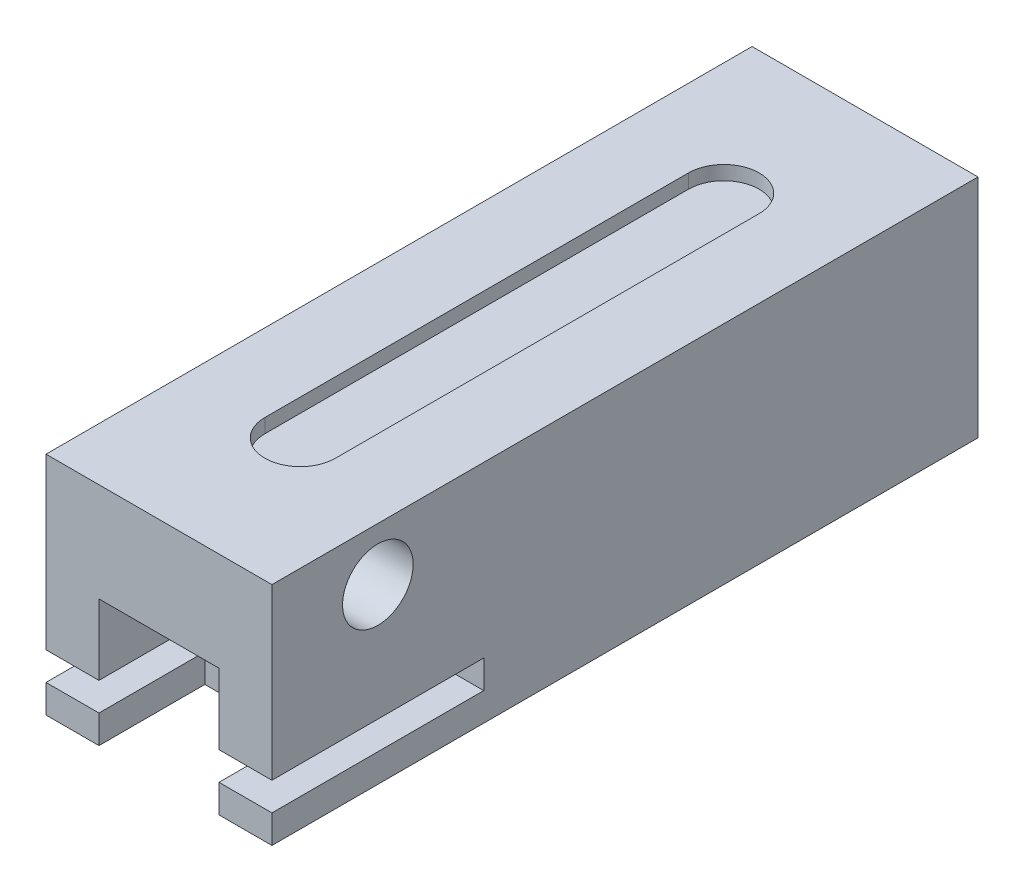
SolidWorks part; units mm, degrees
ref_plane "Front Plane" through (0, 0, 0) normal (0, 0, 1) x (1, 0, 0)
ref_plane "Top Plane" through (0, 0, 0) normal (0, 1, 0) x (1, 0, 0)
ref_plane "Right Plane" through (0, 0, 0) normal (1, 0, 0) x (0, 0, -1)
sketch "Sketch1" plane through (0, 0, 0) normal (0, 0, 1) x (1, 0, 0)
  line L1 (-16, -16) -> (16, -16)
  line L2 (-16, -16) -> (-16, 16)
  line L3 (-16, 16) -> (16, 16)
  line L4 (16, -16) -> (16, 16)
  line L5 (-16, -16) -> (16, 16) construction
  line L6 (-16, 16) -> (16, -16) construction
  point P0 (0, 0)
  dimension "D1" = 32
  dimension "D2" = 32
extrude "Boss-Extrude1" add sketch "Sketch1" against normal blind 100
sketch "Sketch2" plane through (0, 0, 0) normal (0, 1, 0) x (1, 0, 0)
  line L0 (0, 20) -> (0, 0) construction
  line L1 (0, 20) -> (0, 80) construction
  line L2 (5, 80) -> (5, 20)
  line L3 (-5, 80) -> (-5, 20)
  circle A0 centre (0, 20) radius 5
  circle A1 centre (0, 80) radius 5
  point P10 (-11.9537, 28.2218)
  point P11 (11.5572, 27.3906)
  point P12 (0, 0)
  dimension "D1" = 10
  dimension "D2" = 10
  dimension "D3" = 20
  dimension "D4" = 60
extrude "Cut-Extrude1" cut sketch "Sketch2" against normal blind 2 from surface contours A1 L3 A0 L2 | A1 | A0 region at (0, 0, -80) region at (0, 0, -50) region at (0, 0, -20) starting at face at (0, 16, -50)
sketch "Sketch3" plane through (0, 0, 0) normal (0, 0, 1) x (1, 0, 0)
  line L0 (-16, 16) -> (-16, -16) construction
  line L1 (-16, -8) -> (16, -8)
  line L2 (-16, -8) -> (-16, -12)
  line L3 (-16, -12) -> (16, -12)
  line L4 (16, -8) -> (16, -12)
  line L5 (16, -16) -> (16, 16) construction
  line L6 (0, -22.0014) -> (0, -12) construction
  line L7 (-8.5, -12) -> (8.5, -12)
  line L8 (-8.5, -12) -> (-8.5, -22.0014)
  line L9 (-8.5, -22.0014) -> (8.5, -22.0014)
  line L10 (8.5, -12) -> (8.5, -22.0014)
  line L11 (-16, -16) -> (16, -16) construction
  line L12 (-8.5, -8) -> (8.5, -8)
  line L13 (-8.5, -8) -> (-8.5, 2)
  line L14 (-8.5, 2) -> (8.5, 2)
  line L15 (8.5, -8) -> (8.5, 2)
  point P14 (0, -12)
  dimension "D1" = 4
  dimension "D2" = 17
  dimension "D3" = 10
  dimension "D4" = 4
extrude "Cut-Extrude2" cut sketch "Sketch3" against normal blind 30 contours L1 L15 L14 L13 | L4 L1 L2 L3 L7 region at (0, -10, 0) region at (0, -3, 0)
extrude "Cut-Extrude4" cut sketch "Sketch3<4>" against normal blind 15 contours L6 L9 L10 L7 | L9 L6 L3 L8 region at (-4.25, -17.0007, 0) region at (4.25, -17.0007, 0)
sketch "Sketch3<4>" plane through (0, 0, 0) normal (0, 0, 1) x (1, 0, 0) same geometry as "Sketch3"
sketch "Sketch4" plane through (0, 0, 0) normal (1, 0, 0) x (0, 0, -1)
  line L0 (100, 16) -> (0, 16) construction
  line L1 (0, -8) -> (0, 16) construction
  circle A0 centre (15, 8.5) radius 5
  circle A1 centre (15, 8.5) radius 7.5
  dimension "D1" = 10
  dimension "D2" = 15
  dimension "D3" = 15
extrude "Cut-Extrude3" cut sketch "Sketch4" against normal through all both and the other way through all contours A0 region at (0, 8.5, -15)
